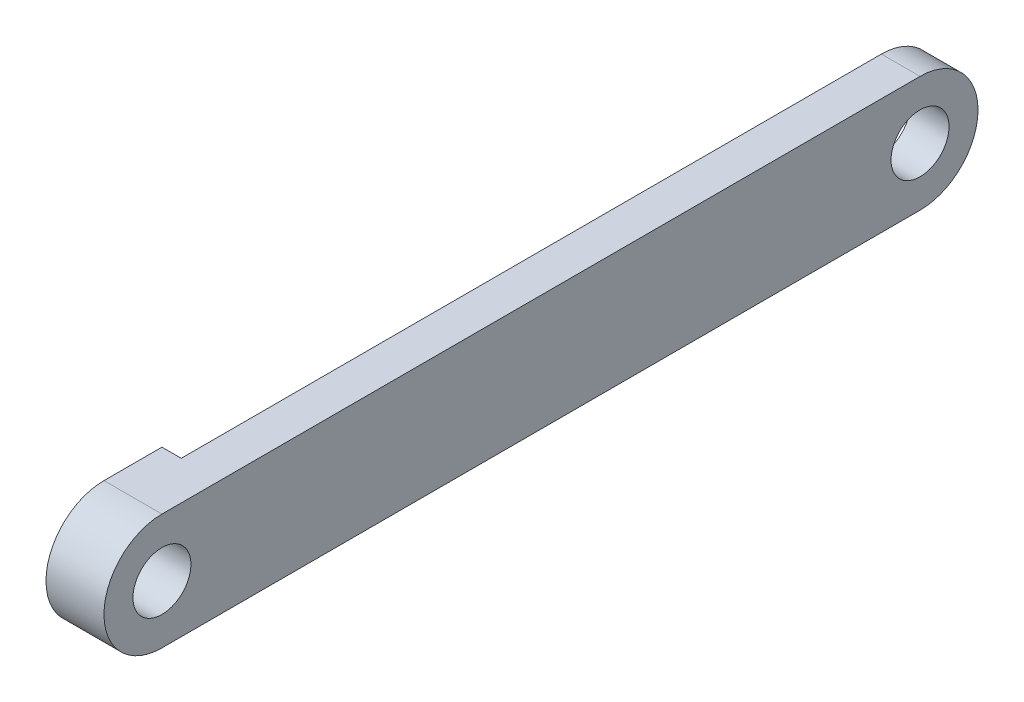
SolidWorks part; units mm, degrees
ref_plane "Front Plane" through (0, 0, 0) normal (0, 0, 1) x (1, 0, 0)
ref_plane "Top Plane" through (0, 0, 0) normal (0, 1, 0) x (1, 0, 0)
ref_plane "Right Plane" through (0, 0, 0) normal (1, 0, 0) x (0, 0, -1)
sketch "Sketch1" plane through (0, 0, 0) normal (1, 0, 0) x (0, 0, -1)
  line L0 (0, 0) -> (39.234, 0) construction
  line L1 (0, -3) -> (39.234, -3)
  line L18 (0, 3) -> (39.234, 3)
  arc A10 (0, -3) -> (0, 3) centre (0, 0) cw
  arc A11 (39.234, 3) -> (39.234, -3) centre (39.234, 0) cw
  circle A12 centre (0, 0) radius 1.5
  circle A13 centre (39.234, 0) radius 1.5
  dimension "D4" = 3
  dimension "D1" = 3
  dimension "D3" = 39.234
  dimension "D2" = 3
extrude "Boss-Extrude1" add sketch "Sketch1" along normal blind 3
sketch "Sketch2" plane through (0, 0, 0) normal (-1, 0, 0) x (0, 0, 1)
  line L0 (0, -3) -> (-39.234, -3) construction
  line L1 (-42.234, 3) -> (-3, 3)
  line L2 (-42.234, 3) -> (-42.234, -3)
  line L3 (-42.234, -3) -> (-3, -3)
  line L4 (-3, 3) -> (-3, -3)
  line L5 (-39.234, 3) -> (0, 3) construction
  arc A0 (0, -3) -> (0, 3) centre (0, 0) ccw construction
  arc A1 (-39.234, 3) -> (-39.234, -3) centre (-39.234, 0) ccw construction
  point P9 (3, 0)
  dimension "D1" = 6
extrude "Cut-Extrude1" cut sketch "Sketch2" against normal blind 1 contours L1 L4 L3 L2
